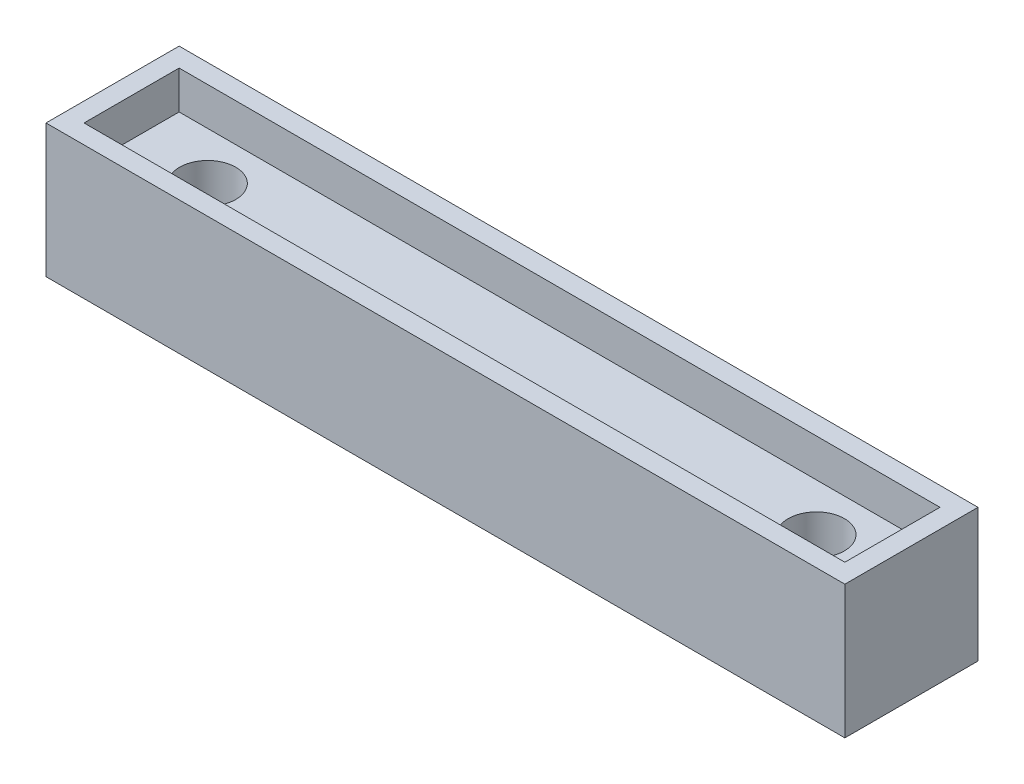
SolidWorks part; units mm, degrees
ref_plane "Front Plane" through (0, 0, 0) normal (0, 0, 1) x (1, 0, 0)
ref_plane "Top Plane" through (0, 0, 0) normal (0, 1, 0) x (1, 0, 0)
ref_plane "Right Plane" through (0, 0, 0) normal (1, 0, 0) x (0, 0, -1)
sketch "Sketch1" plane through (0, 0, 0) normal (0, 1, 0) x (1, 0, 0)
  line L0 (6.8056, 28.3123) -> (65.3062, -8.2429) construction
  line L1 (0, 7) -> (42, 7)
  line L2 (0, 7) -> (0, 0)
  line L3 (0, 0) -> (42, 0)
  line L4 (42, 7) -> (42, 0)
  line L5 (42, 0) -> (44.8404, 4.5455) construction
  dimension "D1" = 7
  dimension "D2" = 42
  dimension "D3" = 32
  dimension "D4" = 5.36
extrude "Riser" add sketch "Sketch1" along normal blind 7
sketch "Sketch2" plane through (0, 0, 0) normal (0, -1, 0) x (1, 0, 0)
  line L0 (0, -7) -> (0, 0) construction
  line L1 (21, 0) -> (21, -7) construction
  line L2 (0, 0) -> (42, 0) construction
  line L3 (42, -7) -> (0, -7) construction
  circle A0 centre (5, -3.5) radius 1.475
  circle A1 centre (37, -3.5) radius 1.475
  point P6 (0, -3.5)
  dimension "D2" = 2.95
  dimension "D1" = 5
extrude "Mounting Holes" cut sketch "Sketch2" against normal through all
sketch "Sketch3" plane through (0, 7, 0) normal (0, 1, 0) x (1, 0, 0)
  line L0 (41, 6) -> (1, 6)
  line L1 (1, 6) -> (1, 1)
  line L2 (1, 1) -> (41, 1)
  line L3 (41, 1) -> (41, 6)
  line L4 (0, 7) -> (0, 0)
  line L5 (0, 0) -> (42, 0)
  line L6 (42, 0) -> (42, 7)
  line L7 (42, 7) -> (0, 7)
  line L8 (0, 7) -> (0, 0)
  line L9 (0, 0) -> (42, 0)
  line L10 (42, 0) -> (42, 7)
  line L11 (42, 7) -> (0, 7)
  dimension "D1" = 0
  dimension "D2" = 1
extrude "Recess (4-Sides)" cut sketch "Sketch3" against normal blind 2 contours L0 L1 L2 L3
sketch "Sketch4" [suppressed] plane through (0, 7, 0) normal (0, 1, 0) x (1, 0, 0)
  line L0 (0, 0) -> (42, 0) construction
  line L1 (1, 6) -> (41, 6)
  line L2 (1, 6) -> (1, 0)
  line L3 (1, 0) -> (41, 0)
  line L4 (41, 6) -> (41, 0)
  line L5 (0, 7) -> (0, 0) construction
  line L6 (42, 0) -> (42, 7) construction
  line L7 (42, 7) -> (0, 7) construction
  dimension "D1" = 1
  dimension "D2" = 1
  dimension "D3" = 1
extrude "Recess (3-Sides)" [suppressed] cut sketch "Sketch4" against normal blind 2
sketch "Sketch5" [suppressed] plane through (0, 0, 0) normal (0, -1, 0) x (1, 0, 0)
  line L1 (10, -1.5) -> (32, -1.5)
  line L2 (10, -1.5) -> (10, -5.5)
  line L3 (10, -5.5) -> (32, -5.5)
  line L4 (32, -1.5) -> (32, -5.5)
  point P4 (37, -3.5)
  point P5 (5, -3.5)
  point P6 (10, -3.5)
  point P9 (32, -3.5)
  dimension "D1" = 5
  dimension "D2" = 5
  dimension "D3" = 4
extrude "Alignment Tab" [suppressed] add sketch "Sketch5" along normal blind 3.2
